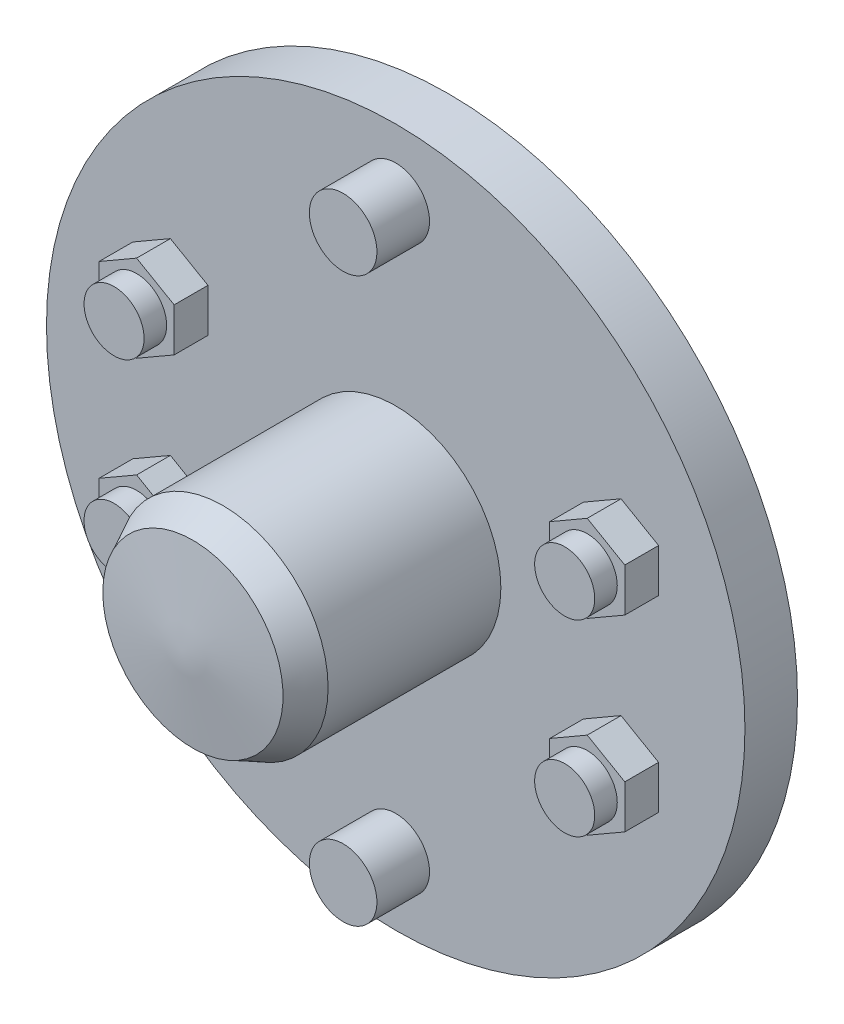
SolidWorks part; units mm, degrees
material "POM Acetal Copolymer"
ref_plane "Front Plane" through (0, 0, 0) normal (0, 0, 1) x (1, 0, 0)
ref_plane "Top Plane" through (0, 0, 0) normal (0, 1, 0) x (1, 0, 0)
ref_plane "Right Plane" through (0, 0, 0) normal (1, 0, 0) x (0, 0, -1)
sketch "Extrude sketch 1" plane through (0, 0, 0) normal (0, 0, 1) x (1, 0, 0)
  circle A0 centre (240, 0) radius 93
  dimension "D1" = 186
extrude "Extrude 1" add sketch "Extrude sketch 1" along normal blind 14 from offset 309 separate body
sketch "Extrude sketch 2" plane through (0, 0, 0) normal (0, 0, 1) x (1, 0, 0)
  circle A0 centre (240, 0) radius 28
  dimension "D1" = 56
extrude "Extrude 2" add sketch "Extrude sketch 2" along normal blind 46 from offset 323 separate body
sketch "Revolve profile 1" plane through (0, 0, 0) normal (0, 1, 0) x (1, 0, 0)
  line L0 (240, -369) -> (268, -369)
  line L1 (268, -369) -> (264, -377)
  line L2 (264, -377) -> (240, -380)
  line L3 (240, -380) -> (240, -369)
  line L4 (240, -364) -> (240, -385) construction
  dimension "D1" = 24
  dimension "D2" = 28
  dimension "D3" = 8
  dimension "D4" = 11
revolve "Revolve 1" add sketch "Revolve profile 1" angle 360 about L4
sketch "Extrude sketch 3" plane through (0, 0, 0) normal (0, 0, 1) x (1, 0, 0)
  line L0 (310, 30.7735) -> (300, 36.547)
  line L1 (300, 36.547) -> (290, 30.7735)
  line L2 (290, 30.7735) -> (290, 19.2265)
  line L3 (290, 19.2265) -> (300, 13.453)
  line L4 (300, 13.453) -> (310, 19.2265)
  line L5 (310, 19.2265) -> (310, 30.7735)
  dimension "D1" = 10
  dimension "D2" = 5.7735
extrude "Extrude 3" add sketch "Extrude sketch 3" along normal blind 9 from offset 323 separate body
sketch "Extrude sketch 4" plane through (0, 0, 0) normal (0, 0, 1) x (1, 0, 0)
  circle A0 centre (300, 25) radius 8
  dimension "D1" = 16
extrude "Extrude 4" add sketch "Extrude sketch 4" along normal blind 6 from offset 332 separate body
sketch "Extrude sketch 5" plane through (0, 0, 0) normal (0, 0, 1) x (1, 0, 0)
  line L0 (310, -19.2265) -> (300, -13.453)
  line L1 (300, -13.453) -> (290, -19.2265)
  line L2 (290, -19.2265) -> (290, -30.7735)
  line L3 (290, -30.7735) -> (300, -36.547)
  line L4 (300, -36.547) -> (310, -30.7735)
  line L5 (310, -30.7735) -> (310, -19.2265)
  dimension "D1" = 10
  dimension "D2" = 5.7735
extrude "Extrude 5" add sketch "Extrude sketch 5" along normal blind 9 from offset 323 separate body
sketch "Extrude sketch 6" plane through (0, 0, 0) normal (0, 0, 1) x (1, 0, 0)
  circle A0 centre (300, -25) radius 8
  dimension "D1" = 16
extrude "Extrude 6" add sketch "Extrude sketch 6" along normal blind 6 from offset 332 separate body
sketch "Extrude sketch 7" plane through (0, 0, 0) normal (0, 0, 1) x (1, 0, 0)
  line L0 (190, 30.7735) -> (180, 36.547)
  line L1 (180, 36.547) -> (170, 30.7735)
  line L2 (170, 30.7735) -> (170, 19.2265)
  line L3 (170, 19.2265) -> (180, 13.453)
  line L4 (180, 13.453) -> (190, 19.2265)
  line L5 (190, 19.2265) -> (190, 30.7735)
  dimension "D1" = 10
  dimension "D2" = 5.7735
extrude "Extrude 7" add sketch "Extrude sketch 7" along normal blind 9 from offset 323 separate body
sketch "Extrude sketch 8" plane through (0, 0, 0) normal (0, 0, 1) x (1, 0, 0)
  circle A0 centre (180, 25) radius 8
  dimension "D1" = 16
extrude "Extrude 8" add sketch "Extrude sketch 8" along normal blind 6 from offset 332 separate body
sketch "Extrude sketch 9" plane through (0, 0, 0) normal (0, 0, 1) x (1, 0, 0)
  line L0 (190, -19.2265) -> (180, -13.453)
  line L1 (180, -13.453) -> (170, -19.2265)
  line L2 (170, -19.2265) -> (170, -30.7735)
  line L3 (170, -30.7735) -> (180, -36.547)
  line L4 (180, -36.547) -> (190, -30.7735)
  line L5 (190, -30.7735) -> (190, -19.2265)
  dimension "D1" = 10
  dimension "D2" = 5.7735
extrude "Extrude 9" add sketch "Extrude sketch 9" along normal blind 9 from offset 323 separate body
sketch "Extrude sketch 10" plane through (0, 0, 0) normal (0, 0, 1) x (1, 0, 0)
  circle A0 centre (180, -25) radius 8
  dimension "D1" = 16
extrude "Extrude 10" add sketch "Extrude sketch 10" along normal blind 6 from offset 332 separate body
sketch "Extrude sketch 11" plane through (0, 0, 0) normal (0, 0, 1) x (1, 0, 0)
  circle A0 centre (240, 75) radius 9
  dimension "D1" = 18
extrude "Extrude 11" add sketch "Extrude sketch 11" along normal blind 14 from offset 323 separate body
sketch "Extrude sketch 12" plane through (0, 0, 0) normal (0, 0, 1) x (1, 0, 0)
  circle A0 centre (240, -75) radius 9
  dimension "D1" = 18
extrude "Extrude 12" add sketch "Extrude sketch 12" along normal blind 14 from offset 323 separate body
combine bodies "Combine (weld / assembly of features)" operation type add bodies to combine 110 104 109 105 111 102 112 108 106 103 113 107 101
